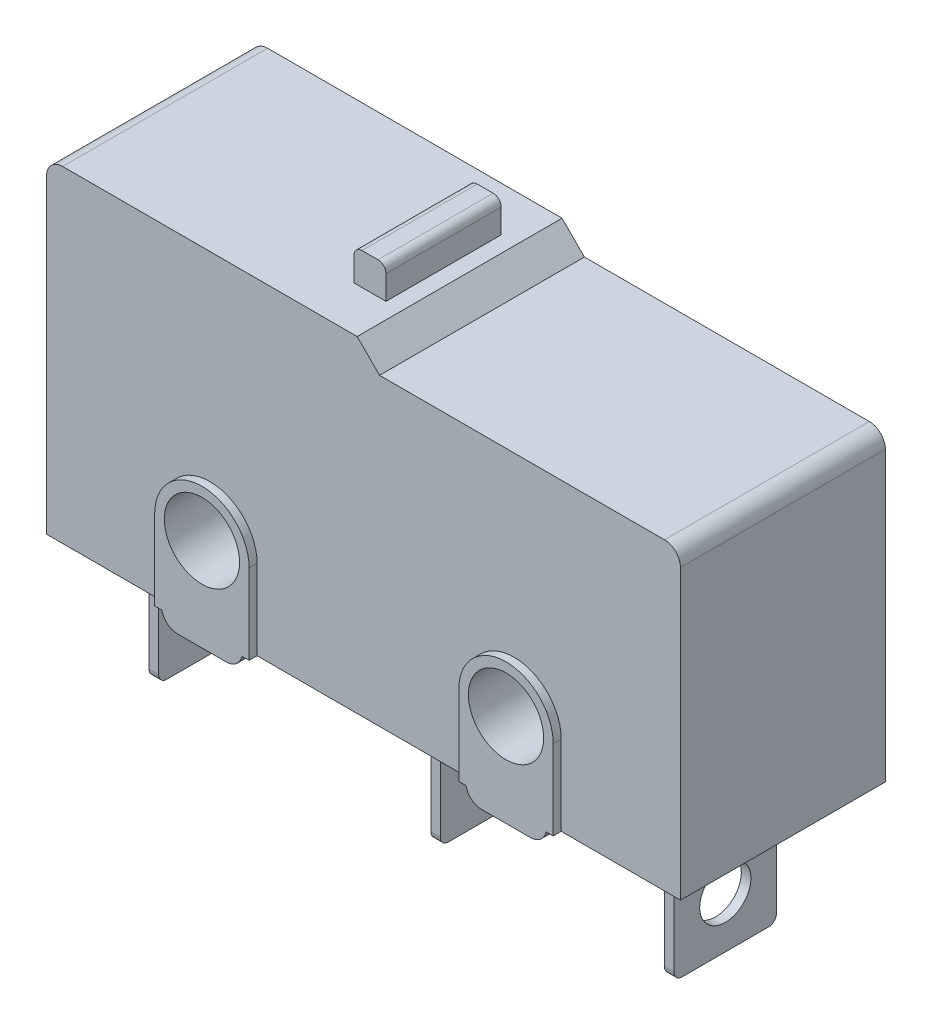
SolidWorks part; units mm, degrees
ref_plane "Front Plane" through (0, 0, 0) normal (0, 0, 1) x (1, 0, 0)
ref_plane "Top Plane" through (0, 0, 0) normal (0, 1, 0) x (1, 0, 0)
ref_plane "Right Plane" through (0, 0, 0) normal (1, 0, 0) x (0, 0, -1)
sketch "Sketch1" plane through (0, 0, 0) normal (0, 0, 1) x (1, 0, 0)
  line L0 (0, 0) -> (-3.95, 0)
  line L1 (-6.45, 0) -> (-6.45, -0.4)
  line L2 (-6.45, -0.4) -> (-3.95, -0.4)
  line L3 (-3.95, -0.4) -> (-3.95, 0)
  line L4 (-6.45, 0) -> (-13.45, 0)
  line L5 (-15.95, 0) -> (-15.95, -0.4)
  line L6 (-15.95, -0.4) -> (-13.45, -0.4)
  line L7 (-13.45, -0.4) -> (-13.45, 0)
  line L9 (-19.8, 0) -> (-19.8, 10.2)
  line L10 (-19.8, 10.2) -> (-10.1, 10.2)
  line L11 (-10.1, 10.2) -> (-9.4, 9.5)
  line L12 (-9.4, 9.5) -> (0, 9.5)
  line L13 (0, 9.5) -> (0, 0)
  line L14 (-14.7, -0.4) -> (-14.7, 2.5) construction
  line L15 (-5.2, -0.4) -> (-5.2, 2.5) construction
  line L16 (-14.7, 2.5) -> (-5.2, 2.5) construction
  line L17 (-15.95, 0) -> (-19.8, 0)
  circle A0 centre (-14.7, 2.5) radius 1.175
  circle A1 centre (-5.2, 2.5) radius 1.175
  point P21 (0, 0)
  dimension "D1" = 2.35
  dimension "D5" = 5.1
  dimension "D2" = 10.2
  dimension "D3" = 9.5
  dimension "D4" = 19.8
  dimension "D6" = 9.5
  dimension "D7" = 2.5
  dimension "D8" = 2.9
  dimension "D9" = 2.5
  dimension "D10" = 10.4
  dimension "D11" = 45
extrude "Boss-Extrude1" add sketch "Sketch1" along normal blind 6.4
sketch "Sketch2" plane through (0, 10.2, 0) normal (0, 1, 0) x (1, 0, 0)
  line L0 (-19.8, -3.2) -> (-10.1, -3.2) construction
  line L1 (-19.8, -6.4) -> (-19.8, 0) construction
  line L2 (-10.1, -6.4) -> (-10.1, 0) construction
  line L4 (-10.6, -5) -> (-11.6, -5)
  line L5 (-10.6, -5) -> (-10.6, -1.4)
  line L6 (-10.6, -1.4) -> (-11.6, -1.4)
  line L7 (-11.6, -5) -> (-11.6, -1.4)
  line L8 (-10.6, -5) -> (-11.6, -1.4) construction
  line L9 (-10.6, -1.4) -> (-11.6, -5) construction
  point P6 (-11.1, -3.2)
  dimension "D1" = 3.6
  dimension "D2" = 1
  dimension "D3" = 0.5
extrude "Boss-Extrude2" add sketch "Sketch2" along normal blind 1
sketch "Sketch3" plane through (0, 0, 0) normal (0, -1, 0) x (1, 0, 0)
  line L0 (-19.8, 3.2) -> (0, 3.2) construction
  line L1 (-19.8, 6.4) -> (-19.8, 0) construction
  line L2 (0, 6.4) -> (0, 0) construction
  line L4 (-17.9, 1.6) -> (-18.2, 1.6)
  line L5 (-17.9, 1.6) -> (-17.9, 4.8)
  line L6 (-17.9, 4.8) -> (-18.2, 4.8)
  line L7 (-18.2, 1.6) -> (-18.2, 4.8)
  line L8 (-17.9, 1.6) -> (-18.2, 4.8) construction
  line L9 (-17.9, 4.8) -> (-18.2, 1.6) construction
  line L10 (-9.1, 1.6) -> (-9.4, 1.6)
  line L11 (-9.1, 1.6) -> (-9.1, 4.8)
  line L12 (-9.1, 4.8) -> (-9.4, 4.8)
  line L13 (-9.4, 1.6) -> (-9.4, 4.8)
  line L14 (-9.1, 1.6) -> (-9.4, 4.8) construction
  line L15 (-9.1, 4.8) -> (-9.4, 1.6) construction
  line L16 (-1.8, 1.6) -> (-2.1, 1.6)
  line L17 (-1.8, 1.6) -> (-1.8, 4.8)
  line L18 (-1.8, 4.8) -> (-2.1, 4.8)
  line L19 (-2.1, 1.6) -> (-2.1, 4.8)
  line L20 (-1.8, 1.6) -> (-2.1, 4.8) construction
  line L21 (-1.8, 4.8) -> (-2.1, 1.6) construction
  point P6 (-18.05, 3.2)
  point P11 (-9.25, 3.2)
  point P16 (-1.95, 3.2)
  dimension "D1" = 3.2
  dimension "D2" = 0.3
  dimension "D3" = 1.6
  dimension "D4" = 8.8
  dimension "D5" = 7.3
extrude "Boss-Extrude3" add sketch "Sketch3" along normal blind 3.9
sketch "Sketch4" plane through (-1.8, 0, 0) normal (1, 0, 0) x (0, 0, -1)
  line L0 (-3.2, 0) -> (-3.2, -3.9) construction
  line L1 (-6.4, 0) -> (0, 0) construction
  line L2 (-1.6, -3.9) -> (-4.8, -3.9) construction
  circle A0 centre (-3.2, -2.3) radius 0.8
  dimension "D1" = 1.6
  dimension "D2" = 1.6
extrude "Cut-Extrude1" cut sketch "Sketch4" against normal through all
sketch "Sketch5" plane through (0, 0, 6.4) normal (0, 0, 1) x (1, 0, 0)
  line L0 (-16.175, 2.5) -> (-16.175, 0)
  line L1 (-19.8, 0) -> (-15.95, 0) construction
  line L2 (-16.175, 0) -> (-15.95, 0)
  line L3 (-15.95, 0) -> (-15.95, -0.4)
  line L4 (-15.95, -0.4) -> (-13.45, -0.4)
  line L5 (-13.45, -0.4) -> (-13.45, 0)
  line L6 (-13.225, 2.5) -> (-13.225, 0)
  line L7 (-13.45, 0) -> (-6.45, 0) construction
  line L8 (-13.225, 0) -> (-13.45, 0)
  line L9 (-6.675, 2.5) -> (-6.675, 0)
  line L10 (-6.675, 0) -> (-6.45, 0)
  line L11 (-6.45, 0) -> (-6.45, -0.4)
  line L12 (-6.45, -0.4) -> (-3.95, -0.4)
  line L13 (-3.95, -0.4) -> (-3.95, 0)
  line L14 (-3.725, 2.5) -> (-3.725, 0)
  line L15 (-3.95, 0) -> (0, 0) construction
  line L16 (-3.725, 0) -> (-3.95, 0)
  circle A9 centre (-14.7, 2.5) radius 1.475
  arc A10 (-13.225, 2.5) -> (-16.175, 2.5) centre (-14.7, 2.5) ccw
  circle A11 centre (-14.7, 2.5) radius 1.175 construction
  circle A12 centre (-5.2, 2.5) radius 1.475
  arc A13 (-3.725, 2.5) -> (-6.675, 2.5) centre (-5.2, 2.5) ccw
  circle A14 centre (-5.2, 2.5) radius 1.175 construction
  circle A15 centre (-14.7, 2.5) radius 1.175
  circle A16 centre (-5.2, 2.5) radius 1.175
  dimension "D1" = 0.3
  dimension "D2" = 0.3
extrude "Boss-Extrude4" add sketch "Sketch5" along normal blind 0.25 and the other way offset from surface (6.65 mm away) 0.25 other way up to face at (-13.525, 2.5, 0)
fillet "Fillet1" radius 0.5 6 edges at (-19.8, 10.2, 3.2) (0, 9.5, 3.2) (-3.95, -0.4, 3.2) (-6.45, -0.4, 3.2) (-13.45, -0.4, 3.2) (-15.95, -0.4, 3.2)
fillet "Fillet2" radius 0.25 6 edges at (-1.95, -3.9, 1.6) (-9.25, -3.9, 1.6) (-18.05, -3.9, 1.6) (-18.05, -3.9, 4.8) (-1.95, -3.9, 4.8) (-9.25, -3.9, 4.8)
fillet "Fillet3" radius 0.25 2 edges at (-11.6, 11.2, 3.2) (-10.6, 11.2, 3.2)
